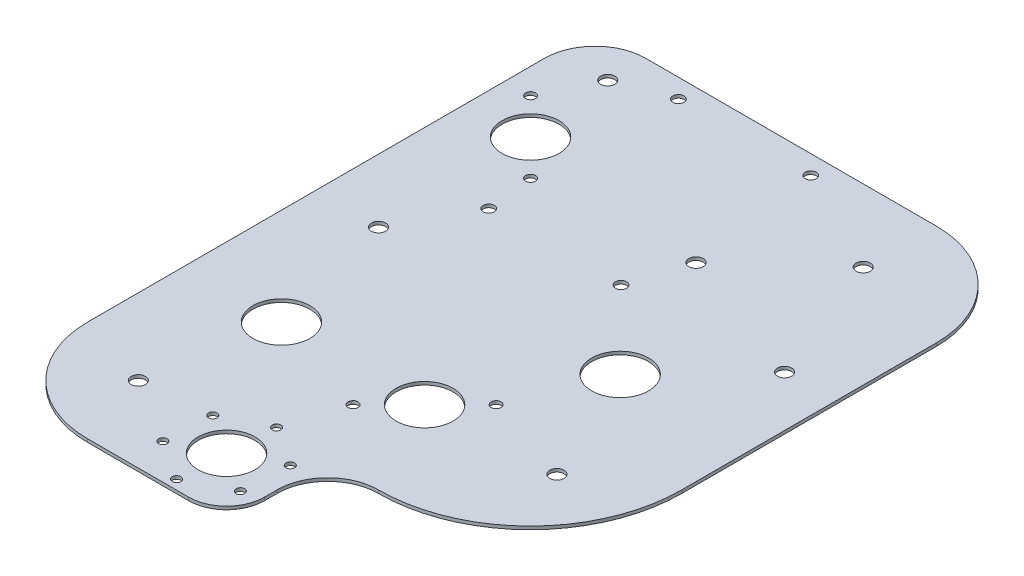
SolidWorks part; units mm, degrees
ref_plane "Front Plane" through (0, 0, 0) normal (0, 0, 1) x (1, 0, 0)
ref_plane "Top Plane" through (0, 0, 0) normal (0, 1, 0) x (1, 0, 0)
ref_plane "Right Plane" through (0, 0, 0) normal (1, 0, 0) x (0, 0, -1)
sketch "Sketch1" plane through (0, 0, 0) normal (0, 1, 0) x (1, 0, 0)
  line L0 (9.4615, 127.3918) -> (111.0615, 25.7918) construction
  line L1 (-111.0615, -127.3918) -> (111.0615, -127.3918)
  line L2 (-111.0615, -127.3918) -> (-111.0615, 127.3918)
  line L3 (-111.0615, 127.3918) -> (111.0615, 127.3918)
  line L4 (111.0615, -127.3918) -> (111.0615, 127.3918)
  line L5 (-111.0615, -127.3918) -> (111.0615, 127.3918) construction
  line L6 (-111.0615, 127.3918) -> (111.0615, -127.3918) construction
  line L7 (111.0615, 127.3918) -> (9.4615, 127.3918) construction
  line L8 (111.0615, 127.3918) -> (111.0615, 25.7918) construction
  line L9 (111.0615, 25.7918) -> (9.4615, 25.7918) construction
  line L10 (9.4615, 127.3918) -> (9.4615, 25.7918) construction
  line L11 (111.0615, 127.3918) -> (9.4615, 25.7918) construction
  line L12 (9.4615, 25.7918) -> (9.4615, -16.4992) construction
  line L13 (-62.4205, -78.7508) -> (9.4615, -78.7508) construction
  line L14 (-8.499, -96.7113) -> (27.422, -60.7903) construction
  circle A0 centre (45.4025, -16.4992) radius 35.941 construction
  circle A1 centre (9.4615, -78.7508) radius 35.941 construction
  circle A2 centre (-62.4205, -78.7508) radius 35.941 construction
  circle A3 centre (9.4615, -78.7508) radius 14.2875
  circle A4 centre (45.4025, -16.4992) radius 14.2875
  circle A5 centre (-62.4205, -78.7508) radius 14.2875
  circle A6 centre (-8.499, -96.7113) radius 1.27
  circle A7 centre (27.422, -60.7903) radius 1.27
  point P0 (0, 0)
  point P9 (60.2615, 76.5918)
  point P13 (45.4025, 19.4418)
  point P18 (-98.3615, -78.7508)
  point P19 (-62.4205, -114.6918)
  point P25 (9.4615, -78.7508)
  dimension "D3" = 71.882
  dimension "D5" = 12.7
  dimension "D7" = 28.575
  dimension "D9" = 2.54
  dimension "D1" = 101.6
  dimension "D2" = 101.6
  dimension "D4" = 6.35
  dimension "D6" = 12.7
  dimension "D8" = 50.8
  dimension "D10" = 45
extrude "Boss-Extrude1" add sketch "Sketch1" along normal blind 1.5875
hole_wizard "#10 Clearance Hole1" positions "Sketch3" profile "Sketch2" hole size "#10" standard "ANSI Inch" end condition through all
sketch "Sketch3" plane through (0, 1.5875, 0) normal (0, 1, 0) x (1, 0, 0)
  point P0 (-8.499, -96.7113)
  point P3 (27.422, -60.7903)
sketch "Sketch2" plane through (-8.499, 1.5875, 96.7113) normal (1, 0, 0) x (0, 0, 1)
  line L0 (0, 0) -> (0, 1.5875)
  line L1 (0, 1.5875) -> (2.4892, 1.5875)
  line L2 (2.4892, 1.5875) -> (2.4892, 0)
  line L5 (2.4892, 0) -> (0, 0)
  line L11 (0, -6.35) -> (0, 107.95) construction
  dimension "Thru Hole Dia." = 4.9784
  dimension "Thru Hole Depth" = 1.5875
sketch "Sketch4" plane through (0, 0, 0) normal (0, -1, 0) x (-1, 0, 0)
  circle A0 centre (59.6925, 117.8668) radius 2.8067
  circle A1 centre (59.6925, 22.6168) radius 2.8067
  circle A2 centre (-6.7335, 117.8668) radius 2.8067
  circle A3 centre (-6.7335, 22.6168) radius 2.8067
  dimension "D1" = 5.6134
extrude "Cut-Extrude1" cut sketch "Sketch4" against normal through all
sketch "Sketch5" plane through (0, 0, 0) normal (0, -1, 0) x (1, 0, 0)
  circle A0 centre (59.7701, -91.1952) radius 1.5875
  dimension "D1" = 3.175
extrude "Cut-Extrude2" cut sketch "Sketch5" against normal through all
sketch "Sketch6" plane through (0, 0, 127.3918) normal (0, 0, 1) x (1, 0, 0)
  line L1 (-111.0615, 0) -> (111.0615, 0)
  line L2 (-111.0615, 0) -> (-111.0615, 1.5875)
  line L3 (-111.0615, 1.5875) -> (111.0615, 1.5875)
  line L4 (111.0615, 0) -> (111.0615, 1.5875)
extrude "Boss-Extrude2" add sketch "Sketch6" along normal blind 50.8
sketch "Sketch7" plane through (0, 0, 0) normal (0, -1, 0) x (-1, 0, 0)
  line L1 (-111.0615, -178.1918) -> (-9.4615, -178.1918)
  line L2 (-111.0615, -178.1918) -> (-111.0615, -127.3918)
  line L3 (-111.0615, -127.3918) -> (-9.4615, -127.3918)
  line L4 (-9.4615, -178.1918) -> (-9.4615, -127.3918)
  dimension "D1" = 101.6
  dimension "D2" = 50.8
extrude "Cut-Extrude3" cut sketch "Sketch7" against normal through all
sketch "Sketch8" plane through (0, 1.5875, 0) normal (0, 1, 0) x (1, 0, 0)
  line L0 (9.4615, -178.1918) -> (9.4615, -127.3918) construction
  line L1 (9.4615, -178.1918) -> (-111.0615, -178.1918) construction
  circle A0 centre (-19.1135, -149.6168) radius 14.2875
  dimension "D1" = 28.575
  dimension "D3" = 28.575
  dimension "D2" = 28.575
extrude "Cut-Extrude5" cut sketch "Sketch8" against normal through all
sketch "Sketch9" plane through (0, 1.5875, 0) normal (0, 1, 0) x (1, 0, 0)
  circle A0 centre (-17.8018, -125.8405) radius 2.15
  circle A1 centre (2.1333, -138.8646) radius 2.15
  circle A2 centre (0.8216, -162.6409) radius 2.15
  circle A3 centre (-20.4252, -173.3932) radius 2.15
  circle A4 centre (-40.3603, -160.3691) radius 2.15
  circle A5 centre (-39.0486, -136.5927) radius 2.15
  dimension "D1" = 4.3
extrude "Cut-Extrude6" cut sketch "Sketch9" against normal through all
sketch "Sketch10" plane through (0, 0, 0) normal (0, -1, 0) x (-1, 0, 0)
  line L0 (62.3578, 46.2822) -> (98.2788, 82.2032) construction
  line L1 (80.3183, 64.2427) -> (13.6345, 64.2427) construction
  line L2 (111.0615, 127.3918) -> (111.0615, -178.1918) construction
  circle A1 centre (80.3183, 64.2427) radius 14.2875
  circle A2 centre (62.3578, 46.2822) radius 1.27
  circle A3 centre (98.2788, 82.2032) radius 1.27
  point P7 (80.3183, 64.2427)
  dimension "D1" = 28.575
  dimension "D4" = 2.54
  dimension "D5" = 30.7432
  dimension "D2" = 50.8
  dimension "D3" = 45
extrude "Cut-Extrude7" cut sketch "Sketch10" against normal through all
hole_wizard "#10 Clearance Hole2" positions "Sketch12" profile "Sketch11" hole size "#10" standard "ANSI Inch" end condition through all
sketch "Sketch12" plane through (0, 0, 0) normal (0, -1, 0) x (-1, 0, 0)
  point P0 (98.2788, 82.2032)
  point P3 (62.3578, 46.2822)
sketch "Sketch11" plane through (-98.2788, 0, -82.2032) normal (1, 0, 0) x (0, 0, -1)
  line L0 (0, 0) -> (0, 1.5875)
  line L1 (0, 1.5875) -> (2.4892, 1.5875)
  line L2 (2.4892, 1.5875) -> (2.4892, 0)
  line L5 (2.4892, 0) -> (0, 0)
  line L11 (0, -6.35) -> (0, 107.95) construction
  dimension "Thru Hole Dia." = 4.9784
  dimension "Thru Hole Depth" = 1.5875
sketch "Sketch13" plane through (0, 1.5875, 0) normal (0, 1, 0) x (1, 0, 0)
  line L2 (111.0615, 127.3918) -> (-111.0615, 127.3918) construction
  line L3 (111.0615, -127.3918) -> (111.0615, 127.3918) construction
  line L4 (60.2615, 127.3918) -> (111.0615, 127.3918)
  line L5 (111.0615, 127.3918) -> (111.0615, 76.5918)
  arc A0 (111.0615, 76.5918) -> (60.2615, 127.3918) centre (60.2615, 76.5918) ccw
  dimension "D1" = 101.6
extrude "Cut-Extrude8" cut sketch "Sketch13" against normal through all
sketch "Sketch14" plane through (0, 1.5875, 0) normal (0, 1, 0) x (1, 0, 0)
  line L0 (111.0615, -127.3918) -> (111.0615, 76.5918) construction
  line L1 (9.4615, -127.3918) -> (111.0615, -127.3918) construction
  line L2 (34.8615, -127.3918) -> (111.0615, -127.3918)
  line L3 (111.0615, -127.3918) -> (111.0615, -51.1918)
  arc A0 (34.8615, -127.3918) -> (111.0615, -51.1918) centre (34.8615, -51.1918) ccw
  dimension "D1" = 152.4
extrude "Cut-Extrude9" cut sketch "Sketch14" against normal through all
fillet "Fillet1" radius 25.4 1 edges at (9.4615, 0.7937, 127.3918)
sketch "Sketch15" plane through (0, 1.5875, 0) normal (0, 1, 0) x (1, 0, 0)
  line L0 (60.2615, 127.3918) -> (-111.0615, 127.3918) construction
  line L1 (-111.0615, 127.3918) -> (-111.0615, -178.1918) construction
  line L2 (-111.0615, 101.9918) -> (-111.0615, 127.3918)
  line L3 (-111.0615, 127.3918) -> (-85.6615, 127.3918)
  arc A0 (-85.6615, 127.3918) -> (-111.0615, 101.9918) centre (-85.6615, 101.9918) ccw
  dimension "D1" = 50.8
extrude "Cut-Extrude10" cut sketch "Sketch15" against normal through all
sketch "Sketch16" plane through (0, 1.5875, 0) normal (0, 1, 0) x (1, 0, 0)
  line L0 (-111.0615, 101.9918) -> (-111.0615, -178.1918) construction
  line L1 (9.4615, -178.1918) -> (-111.0615, -178.1918) construction
  line L2 (-111.0615, -127.3918) -> (-111.0615, -178.1918)
  line L3 (-111.0615, -178.1918) -> (-60.2615, -178.1918)
  arc A0 (-111.0615, -127.3918) -> (-60.2615, -178.1918) centre (-60.2615, -127.3918) ccw
  dimension "D1" = 101.6
extrude "Cut-Extrude11" cut sketch "Sketch16" against normal through all
sketch "Sketch17" plane through (0, 1.5875, 0) normal (0, 1, 0) x (1, 0, 0)
  line L0 (9.4615, -178.1918) -> (9.4615, -152.7918) construction
  line L1 (9.4615, -178.1918) -> (-60.2615, -178.1918) construction
  line L2 (9.4615, -178.1918) -> (9.4615, -159.1418)
  line L3 (9.4615, -178.1918) -> (-9.5885, -178.1918)
  arc A0 (-9.5885, -178.1918) -> (9.4615, -159.1418) centre (-9.5885, -159.1418) ccw
  dimension "D1" = 38.1
extrude "Cut-Extrude13" cut sketch "Sketch17" against normal through all
sketch "Sketch18" plane through (0, 1.5875, 0) normal (0, 1, 0) x (1, 0, 0)
  circle A0 centre (72.9615, -75.8082) radius 1.27
  circle A1 centre (85.6615, 25.7918) radius 1.27
  circle A2 centre (15.8115, 51.1918) radius 1.27
  circle A3 centre (-85.6615, 108.3418) radius 1.27
  circle A4 centre (-79.3115, -13.0918) radius 1.27
  circle A5 centre (-72.9615, -140.0918) radius 1.27
  dimension "D1" = 2.54
extrude "Cut-Extrude14" cut sketch "Sketch18" against normal through all
hole_wizard "1/4 Clearance Hole1" positions "Sketch20" profile "Sketch19" hole size "1/4" standard "ANSI Inch" end condition through all
sketch "Sketch20" plane through (0, 1.5875, 0) normal (0, 1, 0) x (1, 0, 0)
  point P0 (-72.9615, -140.0918)
  point P3 (72.9615, -75.8082)
  point P6 (85.6615, 25.7918)
  point P9 (15.8115, 51.1918)
  point P12 (59.7701, 91.1952)
  point P15 (-79.3115, -13.0918)
  point P18 (-85.6615, 108.3418)
sketch "Sketch19" plane through (-72.9615, 1.5875, 140.0918) normal (1, 0, 0) x (0, 0, 1)
  line L0 (0, 0) -> (0, 1.5875)
  line L1 (0, 1.5875) -> (3.5712, 1.5875)
  line L2 (3.5712, 1.5875) -> (3.5712, 0)
  line L5 (3.5712, 0) -> (0, 0)
  line L11 (0, -6.35) -> (0, 107.95) construction
  dimension "Thru Hole Dia." = 7.1425
  dimension "Thru Hole Depth" = 1.5875
